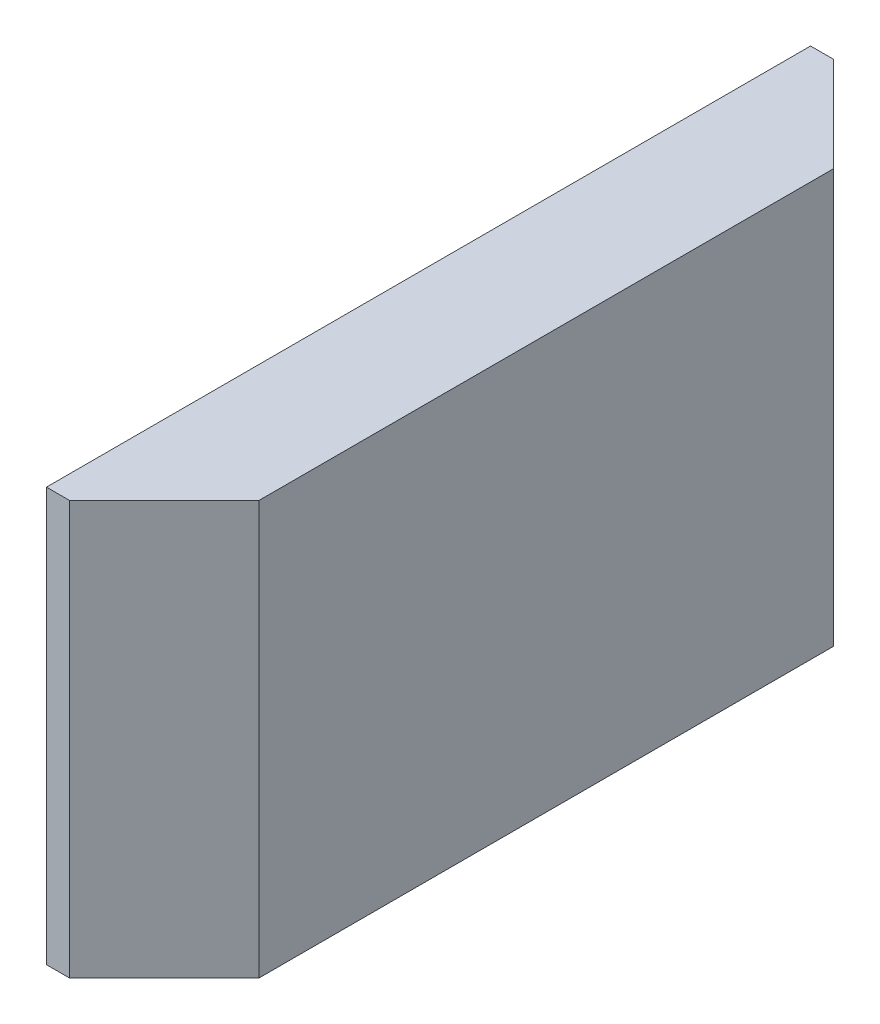
SolidWorks part; units mm, degrees
ref_plane "Front Plane" through (0, 0, 0) normal (0, 0, 1) x (1, 0, 0)
ref_plane "Top Plane" through (0, 0, 0) normal (0, 1, 0) x (1, 0, 0)
ref_plane "Right Plane" through (0, 0, 0) normal (1, 0, 0) x (0, 0, -1)
ref_axis "Axis1" through (0, 0, 0) along (0, 1, 0)
sketch "Sketch1" plane through (0, 0, 0) normal (0, 1, 0) x (1, 0, 0)
  line L0 (0, -100) -> (-33, -133)
  line L1 (0, 0) -> (-41, 0) construction
  line L2 (0, 100) -> (0, -100)
  line L3 (0, 100) -> (-33, 133)
  line L4 (-41, 133) -> (-41, -133)
  line L5 (-41, -133) -> (-33, -133)
  line L6 (-41, 133) -> (-33, 133)
  dimension "D1" = 45
  dimension "D2" = 266
  dimension "D3" = 41
  dimension "D4" = 8
extrude "Boss-Extrude1" add sketch "Sketch1" along normal blind 144
